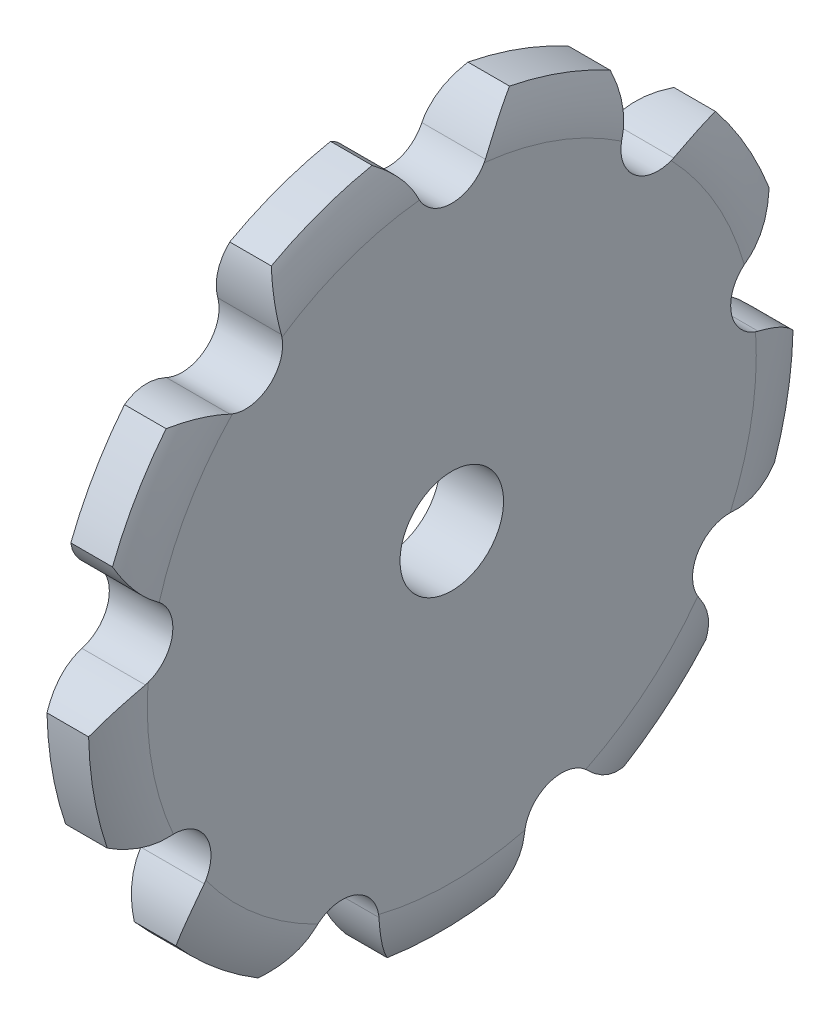
SolidWorks part; units mm, degrees
ref_plane "Plane1" through (0, 0, 0) normal (0, 0, 1) x (1, 0, 0)
ref_plane "Plane2" through (0, 0, 0) normal (0, 1, 0) x (1, 0, 0)
ref_plane "Plane3" through (0, 0, 0) normal (1, 0, 0) x (0, 0, -1)
sketch "Clipboard" plane through (0, 0, 0) normal (0, 1, 0) x (1, 0, 0)
  line L0 (0, 0) -> (25.0873, -3.9734)
  line L1 (-15, 0) -> (100, 0) construction
  line L2 (0, 0) -> (-0.8416, 0.9512)
  line L3 (0, 0) -> (-11.863, 4.5341)
  line L4 (0, 0) -> (3.0618, 0.4849)
  line L5 (0, 0) -> (-2.8109, -1.0484)
  line L6 (0, 0) -> (-6.1032, -4.1179)
  line L7 (-0.8416, 0.9512) -> (9.364, 2.7507)
  line L8 (-76.2, 38.1) -> (-75.2, 38.1)
  line L9 (-73.4361, 41.7391) -> (-72.4443, 41.8673)
  line L10 (-73.4741, 12.7512) -> (-59.5541, 12.7512)
  line L11 (-73.4741, 12.7512) -> (-59.1042, 12.5003)
  line L12 (-147.5013, -35.8225) -> (-147.5932, -35.8997)
  circle A0 centre (0, 0) radius 4.255
  circle A1 centre (0, 0) radius 25
  circle A2 centre (0, 0) radius 25
  dimension "Num_teeth" = 9
  dimension "Thickness" = 7.3625
sketch "BasProSke" plane through (0, 0, 0) normal (0, 1, 0) x (1, 0, 0)
  line L0 (-10, 0) -> (60, 0) construction
  line L1 (0, 0) -> (0, 35.279)
  line L2 (0, 0) -> (7.3625, 0)
  line L3 (7.3625, 0) -> (7.3625, 35.279)
  line L4 (6.0925, 40.8148) -> (1.27, 40.8148)
  arc A0 (0, 35.279) -> (1.27, 40.8148) centre (12.7, 35.279) cw
  arc A1 (7.3625, 35.279) -> (6.0925, 40.8148) centre (-5.3375, 35.279) ccw
  dimension "D1" = 12.7
  dimension "Thickness" = 7.3625
  dimension "Diameter" = 81.6296
revolve "Base-Revolve" add sketch "BasProSke" angle 360 about L0
sketch "TooCutSke" plane through (0, 0, 0) normal (1, 0, 0) x (0, 0, -1)
  line L0 (0, 37.1749) -> (3.8949, 35.3586) construction
  line L1 (0, 0) -> (0, 107) construction
  line L2 (0, 37.1749) -> (-10, 37.1749) construction
  line L3 (0, 37.1749) -> (-3.8949, 35.3586) construction
  arc A0 (3.8949, 35.3586) -> (7.9688, 40.0395) centre (14.0756, 30.6113) cw
  arc A1 (3.8949, 35.3586) -> (-3.8949, 35.3586) centre (0, 37.1749) cw
  arc A2 (-3.8949, 35.3586) -> (-7.9688, 40.0395) centre (-14.0756, 30.6113) ccw
  arc A3 (7.9688, 40.0395) -> (-7.9688, 40.0395) centre (0, 0) ccw
extrude "ToothCut" cut sketch "TooCutSke" along normal through all
pattern_circular "TeethCuts" count 9 every 40 about axis through (-10, 0, 0) along (1, 0, 0) of "ToothCut"
sketch "HubNeaOneSke" plane through (0, 0, 0) normal (-1, 0, 0) x (0, 0, 1)
  circle A0 centre (0, 0) radius 25
  dimension "Diameter" = 50
extrude "HubNearOne" [suppressed] add sketch "HubNeaOneSke" along normal blind 3.0005
fillet "HubNearOneFillet" [suppressed] radius 1
sketch "HubNeaBotSke" plane through (0, 0, 0) normal (-1, 0, 0) x (0, 0, 1)
  circle A0 centre (0, 0) radius 25
  dimension "Diameter" = 50
extrude "HubNearBoth" [suppressed] add sketch "HubNeaBotSke" along normal blind 1.5003
fillet "HubNearBothFillet" [suppressed] radius 1
ref_plane "FarPln" through (7.3625, 0, 0) normal (1, 0, 0) x (0, 0, -1)
sketch "HubFarSke" plane through (7.3625, 0, 0) normal (1, 0, 0) x (0, 0, -1)
  circle A0 centre (0, 0) radius 25
  dimension "Diameter" = 50
extrude "HubFar" [suppressed] add sketch "HubFarSke" along normal blind 1.5003
fillet "HubFarFillet" [suppressed] radius 1
sketch "BorSke" plane through (0, 0, 0) normal (1, 0, 0) x (0, 0, -1)
  circle A0 centre (0, 0) radius 6
  dimension "Diameter" = 12
extrude "Bore" cut sketch "BorSke" along normal mid plane 20.726
sketch "KeySke" plane through (0, 0, 0) normal (1, 0, 0) x (0, 0, -1)
  line L0 (-1, 0) -> (-1, 7)
  line L1 (-1, 7) -> (1, 7)
  line L2 (1, 7) -> (1, 0)
  line L3 (0, 0) -> (0, 34) construction
  line L4 (-1, 0) -> (1, 0)
  dimension "Width" = 2
extrude "Keyway" [suppressed] cut sketch "KeySke" along normal mid plane 20.726
pattern_circular "Keyway2" [suppressed] count 2 every 90 about axis through (-10, 0, 0) along (1, 0, 0)
equation "' \"Pitch@Clipboard\" = 25.4"
equation "' \"Num_teeth@Clipboard\" = 9"
equation "' \"Hub_dia@Clipboard\" = 50"
equation "' \"Overall_len@Clipboard\" = 3"
equation "' \"Diameter@BorSke\" = 12"
equation "' \"T_dim@Clipboard\" = 1"
equation "' \"Width@KeySke\" = 2"
equation "' \"Dr@Clipboard\" = 8.51"
equation "' \"Face_width@Clipboard\" = 7.3625"
equation "' \"Side_radius@Clipboard\" = 12.7"
equation "' \"Side_relief@Clipboard\" = 1.27"
equation "' \"Show_teeth@Clipboard\" = 9"
equation "' \"Fillet_rad@Clipboard\" = 1"
equation "' \"Plate_wid@Clipboard\" = 11.8"
equation "'  \"Cut@Clipboard\" = 1"
equation "'  \"GapAngle@Clipboard\" = 140"
equation "'  \"GapFactor@Clipboard\" = 0.12"
equation "' \"Num_teeth@Clipboard\" = int( \"Num_teeth@Clipboard\" )"
equation "\"Num_teeth@Clipboard\" = ((sgn( \"Num_teeth@Clipboard\" - 5.0)+1)*( \"Num_teeth@Clipboard\" - 5.0))/2 +5.0"
equation "\"Num_teeth@Clipboard\" = ((sgn( \"Num_teeth@Clipboard\" - 200.0)-1)*( \"Num_teeth@Clipboard\" - 200.0))/-2 +200.0"
equation "\"MHD@Clipboard\" = \"Pitch@Clipboard\" * (1.0 / tan(3.14159265 / \"Num_teeth@Clipboard\" )) - 1.05 * \"Plate_wid@Clipboard\" - 2.0 * \"Fillet_rad@Clipboard\" - 1.0"
equation "\"Thickness@Clipboard\"  = \"Face_width@Clipboard\" + (\"Num_strands@Clipboard\" - 1) * \"Transv_pitch@Clipboard\""
equation "\"OAL@Clipboard\" = \"Thickness@Clipboard\" + 2 * \"Fillet_rad@Clipboard\" + 1"
equation "\"MHD@Clipboard\" = ((sgn( \"MHD@Clipboard\" - \"Hub_dia@Clipboard\" )-1)*( \"MHD@Clipboard\" - \"Hub_dia@Clipboard\" ))/-2+ \"Hub_dia@Clipboard\""
equation "\"OAL@Clipboard\" = ((sgn( \"OAL@Clipboard\" - \"Overall_len@Clipboard\" )+1)*( \"OAL@Clipboard\" - \"Overall_len@Clipboard\" ))/2 + \"Overall_len@Clipboard\" + 0.0005"
equation "\"Num_teeth@TeethCuts\" = int( \"Show_teeth@Clipboard\" ) + 1"
equation "\"Num_teeth@TeethCuts\" = ((sgn( \"Num_teeth@TeethCuts\" - \"Num_teeth@Clipboard\" )-1)*( \"Num_teeth@TeethCuts\" - \"Num_teeth@Clipboard\" ))/-2+ \"Num_teeth@Clipboard\""
equation "\"Num_teeth@TeethCuts\" = ((sgn( \"Num_teeth@TeethCuts\" - 2.0)+1)*( \"Num_teeth@TeethCuts\" - 2.0))/2 +2.0"
equation "\"Angle@TeethCuts\" = 360.0 / \"Num_teeth@Clipboard\""
equation "\"Num_teeth@TeethCuts\" = \"Num_teeth@TeethCuts\" * \"Cut@Clipboard\""
equation "\"Angle@TeethCuts\" = \"Angle@TeethCuts\" / \"Cut@Clipboard\""
equation "\"Seat_radius@TooCutSke\" = ( \"Pitch@Clipboard\" / 2.0) / sin(3.14159265 / \"Num_teeth@Clipboard\" ) - \"Dr@Clipboard\" / 2.0 + \"Dr@Clipboard\" * 0.505"
equation "\"R1@TooCutSke\"  = \"Dr@Clipboard\" * 0.505"
equation "\"X@TooCutSke\" = \"GapAngle@Clipboard\" - (90.0 / \"Num_teeth@Clipboard\")"
equation "\"R2@TooCutSke\" = \"GapFactor@Clipboard\"  * \"Dr@Clipboard\" * ( \"Num_teeth@Clipboard\" + 2.0)"
equation "' \"R2@TooCutSke\" = 0.008 * \"Dr@Clipboard\" * ( \"Num_teeth@Clipboard\" * \"Num_teeth@Clipboard\" + 180)"
equation "\"Overcut@TooCutSke\" = 0.01 + 0.625 / 2 * \"Pitch@Clipboard\" - 0.5 * \"Dr@Clipboard\"  +  \"Pitch@Clipboard\" / 2.0 / sin(3.14159265 / \"Num_teeth@Clipboard\" )"
equation "\"Diameter@BasProSke\" = 2.0 * ( 0.625 / 2 * \"Pitch@Clipboard\" - 0.5 * \"Dr@Clipboard\"  +  \"Pitch@Clipboard\" / 2.0 / sin(3.14159265 / \"Num_teeth@Clipboard\" ))"
equation "\"Thickness@BasProSke\"  = \"Thickness@Clipboard\""
equation "\"G1@BasProSke\" =  \"Side_relief@Clipboard\""
equation "\"G2@BasProSke\" =  \"Side_relief@Clipboard\""
equation "\"D1@BasProSke\" =  \"Side_radius@Clipboard\""
equation "\"Diameter@HubNeaOneSke\" = \"MHD@Clipboard\""
equation "\"Length@HubNearOne\" = \"OAL@Clipboard\" - \"Thickness@BasProSke\""
equation "\"Diameter@HubNeaBotSke\" = \"MHD@Clipboard\""
equation "\"Length@HubNearBoth\" = ( \"OAL@Clipboard\" - \"Thickness@BasProSke\" ) / 2.0"
equation "\"D1@HubNearOneFillet\" = \"Fillet_rad@Clipboard\""
equation "\"D1@HubNearBothFillet\" = \"Fillet_rad@Clipboard\""
equation "\"Thickness@FarPln\" = \"Thickness@BasProSke\""
equation "\"Diameter@HubFarSke\" = \"MHD@Clipboard\""
equation "\"Length@HubFar\" = ( \"OAL@Clipboard\" - \"Thickness@BasProSke\" ) / 2.0"
equation "\"D1@HubFarFillet\" = \"Fillet_rad@Clipboard\""
equation "\"D1@Bore\" = \"OAL@Clipboard\" * 2.0"
equation "\"D1@Keyway\" = \"OAL@Clipboard\" * 2.0"
equation "\"Offset@KeySke\" = \"T_dim@Clipboard\" + \"Diameter@BorSke\" / 2.0"
